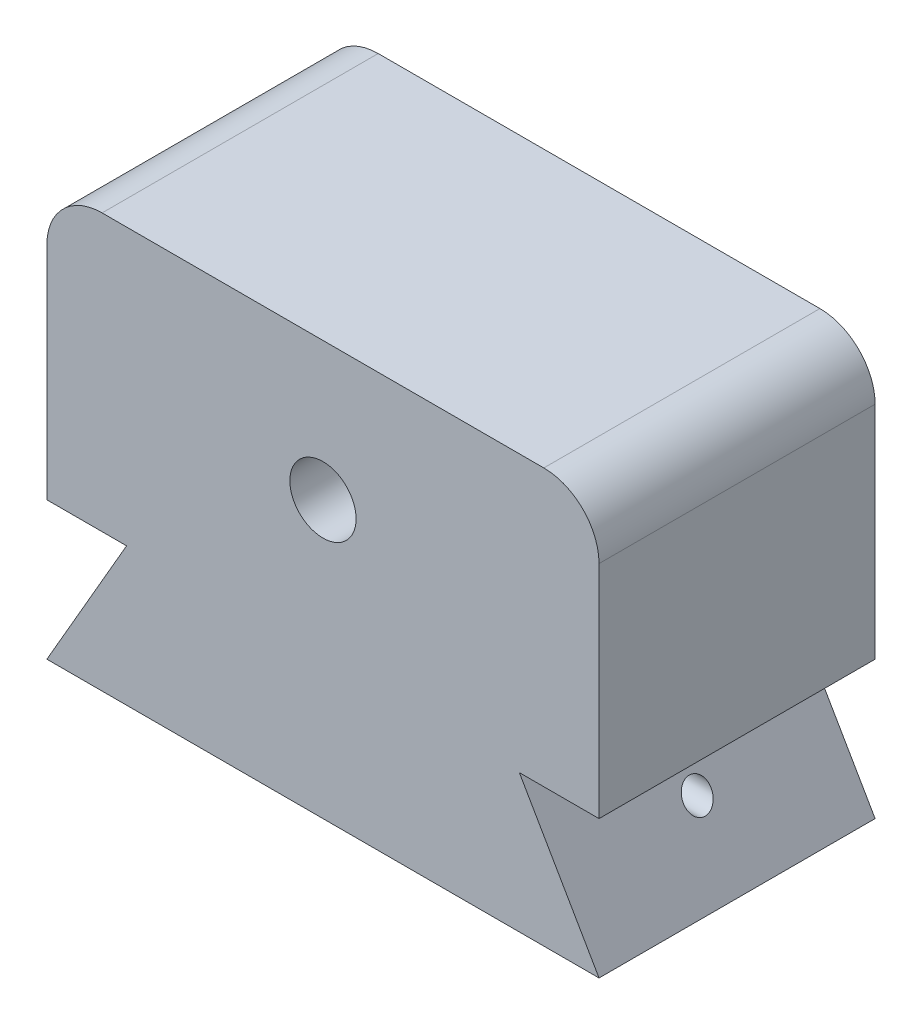
SolidWorks part; units mm, degrees
ref_plane "Front Plane" through (0, 0, 0) normal (0, 0, 1) x (1, 0, 0)
ref_plane "Top Plane" through (0, 0, 0) normal (0, 1, 0) x (1, 0, 0)
ref_plane "Right Plane" through (0, 0, 0) normal (1, 0, 0) x (0, 0, -1)
sketch "Sketch1" plane through (0, 0, 0) normal (0, 0, 1) x (1, 0, 0)
  line L0 (-50, 0) -> (50, 0)
  line L1 (50, 0) -> (35.5662, 25)
  line L2 (35.5662, 25) -> (-35.5662, 25)
  line L3 (-35.5662, 25) -> (-50, 0)
  line L4 (-50, 25) -> (50, 25)
  line L5 (-50, 25) -> (-50, 65)
  line L6 (-40, 75) -> (40, 75)
  line L7 (50, 65) -> (50, 25)
  circle A0 centre (0, 50) radius 6
  arc A1 (50, 65) -> (40, 75) centre (40, 65) ccw
  arc A2 (-50, 65) -> (-40, 75) centre (-40, 65) cw
  point P4 (0, 25)
  point P7 (0, 0)
  dimension "D5" = 12
  dimension "D10" = 10
  dimension "D1" = 60
  dimension "D2" = 120
  dimension "D3" = 100
  dimension "D4" = 25
  dimension "D6" = 50
  dimension "D7" = 50
  dimension "D8" = 25
  dimension "D9" = 25
extrude "Boss-Extrude1" add sketch "Sketch1" along normal blind 50 contours L2 L3 L0 L1 | L7 L6 L5 L4 L2 A0 region at (0, 11.7971, 0) region at (-42.7831, 26.118, 0)
sketch "Sketch2" plane through (0, 0, 0) normal (0, -1, 0) x (1, 0, 0)
  line L0 (-50, 25) -> (50, 25) construction
  line L1 (-50, 50) -> (-50, 0) construction
  line L2 (50, 50) -> (50, 0) construction
  line L3 (0, 50) -> (0, 0) construction
  line L4 (-50, 50) -> (50, 50) construction
  circle A0 centre (0, 25) radius 6
  dimension "D1" = 12
extrude "Cut-Extrude1" cut sketch "Sketch2" against normal up to surface (25 mm away) up to face at (42.7831, 25, 25)
sketch "Sketch3" plane through (0, 0, 0) normal (1, 0, 0) x (0, 0, -1)
  line L0 (-25, -1000) -> (-25, 49000) construction
  line L1 (-50, 0) -> (0, 0) construction
  line L2 (-1050, 12.5) -> (48950, 12.5) construction
  line L3 (-50, 0) -> (-50, 25) construction
  line L4 (-50, 25) -> (0, 25) construction
  circle A0 centre (-25, 12.5) radius 2.5
  point P7 (-25, 0)
  point P13 (-50, 12.5)
  dimension "D1" = 5
  dimension "D2" = 12.5
extrude "Cut-Extrude2" cut sketch "Sketch3" against normal up to surface and the other way up to surface up to face at (-42.7831, 12.5, 25) other way up to face at (42.7831, 12.5, 25)
equation "\"PendulumLength\"= 140mm"
equation "\"EncoderOuterDiameter\"=1.5"
equation "\"EncoderShaftDiameter\"= 6mm"
equation "\"EncoderShaftLength\"=15mm+.5in+3mm"
equation "\"ShaftDiameter\"= 12mm"
equation "\"PendulumHolderangle\"=60"
equation "\"PendulumholderBottomHeight\"= 75"
equation "\"PendulumholderBottomWidth\"= 75"
equation "\"PendulumholderHeight\"=25"
equation "\"BearingOutsideDiameter\"=21mm"
equation "\"D4@Sketch1\"=\"PendulumholderHeight\""
equation "\"D1@Sketch1\"=\"PendulumHolderangle\""
equation "\"PendulumHolderWidth\"= 100mm"
equation "\"D3@Sketch1\"=\"PendulumHolderWidth\""
equation "\"PendulumDiameter\"=12mm"
equation "\"D1@Sketch2\"=\"PendulumDiameter\""
equation "\"D5@Sketch1\"=\"ShaftDiameter\""
